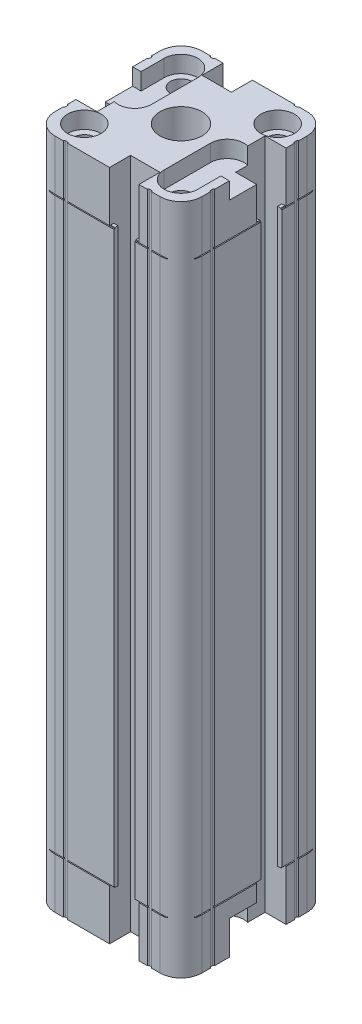
SolidWorks part; units mm, degrees
ref_plane "Front Plane" through (0, 0, 0) normal (0, 0, 1) x (1, 0, 0)
ref_plane "Top Plane" through (0, 0, 0) normal (0, 1, 0) x (1, 0, 0)
ref_plane "Right Plane" through (0, 0, 0) normal (1, 0, 0) x (0, 0, -1)
sketch "Sketch1" plane through (0, 0, 0) normal (0, 1, 0) x (1, 0, 0)
  line L1 (0, 0) -> (35, 0)
  line L2 (0, 0) -> (0, 35)
  line L3 (0, 35) -> (35, 35)
  line L4 (35, 0) -> (35, 35)
  dimension "D1" = 35
  dimension "D2" = 35
extrude "Boss-Extrude1" add sketch "Sketch1" along normal blind 160
sketch "Sketch2" plane through (0, 0, 0) normal (0, -1, 0) x (-1, 0, 0)
  line L0 (0, 0) -> (-35, 0) construction
  line L1 (0, 35) -> (0, 0) construction
  line L2 (-29, 6) -> (-29, 17) construction
  line L3 (-33, 6) -> (-33, 17)
  line L4 (-25, 6) -> (-25, 17)
  line L5 (-35, 0) -> (-35, 35) construction
  line L6 (-35, 35) -> (0, 35) construction
  line L7 (-6, 18) -> (-6, 29) construction
  line L8 (-10, 18) -> (-10, 29)
  line L9 (-2, 18) -> (-2, 29)
  circle A0 centre (-6, 6) radius 4
  circle A1 centre (-29, 29) radius 4
  arc A2 (-33, 6) -> (-25, 6) centre (-29, 6) ccw
  arc A3 (-25, 17) -> (-33, 17) centre (-29, 17) ccw
  arc A4 (-10, 18) -> (-2, 18) centre (-6, 18) ccw
  arc A5 (-2, 29) -> (-10, 29) centre (-6, 29) ccw
  point P10 (-29, 11.5)
  point P21 (-6, 23.5)
  dimension "D1" = 8
  dimension "D4" = 4
  dimension "D5" = 11
  dimension "D10" = 4
  dimension "D11" = 6
  dimension "D2" = 6
  dimension "D3" = 6
  dimension "D6" = 6
  dimension "D7" = 6
  dimension "D8" = 6
  dimension "D9" = 11
extrude "Cut-Extrude1" cut sketch "Sketch2" against normal blind 8
sketch "Sketch3" plane through (0, 0, 0) normal (0, -1, 0) x (-1, 0, 0)
  line L0 (0, 35) -> (0, 0) construction
  line L1 (-5, 23.5) -> (0, 23.5)
  line L2 (-5, 23.5) -> (-5, 14.127)
  line L3 (-5, 14.127) -> (0, 14.127)
  line L4 (0, 23.5) -> (0, 14.127)
  line L5 (-2, 18) -> (-2, 29) construction
  line L6 (-35, 20.873) -> (-30, 20.873)
  line L7 (-35, 20.873) -> (-35, 11.5)
  line L8 (-35, 11.5) -> (-30, 11.5)
  line L9 (-30, 20.873) -> (-30, 11.5)
  line L10 (-35, 0) -> (-35, 35) construction
  line L11 (-33, 17) -> (-33, 6) construction
  arc A2 (-25, 17) -> (-33, 17) centre (-29, 17) ccw construction
  arc A3 (-10, 18) -> (-2, 18) centre (-6, 18) ccw construction
  point P13 (-2, 23.5)
  point P25 (-32.5, 20.873)
  point P34 (-33, 11.5)
  dimension "D1" = 5
  dimension "D2" = 5
extrude "Cut-Extrude2" cut sketch "Sketch3" against normal up to surface (8 mm away) up to face at (6, 8, -23.5)
sketch "Sketch5" plane through (0, 0, 0) normal (0, -1, 0) x (1, 0, 0)
  line L0 (35, -20.873) -> (35, -35) construction
  line L1 (5, -17) -> (0, -17)
  line L2 (5, -17) -> (5, -10)
  line L3 (5, -10) -> (0, -10)
  line L4 (0, -17) -> (0, -10)
  line L5 (30, -18) -> (35, -18)
  line L6 (30, -18) -> (30, -25)
  line L7 (30, -25) -> (35, -25)
  line L8 (35, -18) -> (35, -25)
  line L9 (0, 0) -> (35, 0) construction
  line L10 (18, 0) -> (25, 0)
  line L11 (18, 0) -> (18, -5)
  line L12 (18, -5) -> (25, -5)
  line L13 (25, 0) -> (25, -5)
  line L14 (35, -35) -> (0, -35) construction
  line L15 (10, -35) -> (17, -35)
  line L16 (10, -35) -> (10, -30)
  line L17 (10, -30) -> (17, -30)
  line L18 (17, -35) -> (17, -30)
  circle A0 centre (6, -6) radius 4 construction
  circle A1 centre (29, -29) radius 4 construction
  dimension "D1" = 7
  dimension "D2" = 7
  dimension "D3" = 5
  dimension "D4" = 7
  dimension "D5" = 10
  dimension "D6" = 7
  dimension "D7" = 5
  dimension "D8" = 10
extrude "Cut-Extrude3" cut sketch "Sketch5" against normal blind 12
sketch "Sketch6" plane through (0, 12, 0) normal (0, -1, 0) x (1, 0, 0)
  line L6 (0, -16) -> (1, -16)
  line L7 (0, -10) -> (0, -17) construction
  line L8 (1, -16) -> (1, -17)
  line L9 (0, -17) -> (5, -17) construction
  line L10 (1, -17) -> (5, -17)
  line L11 (5, -17) -> (5, -10)
  line L12 (5, -10) -> (1, -10)
  line L13 (5, -10) -> (0, -10) construction
  line L14 (1, -10) -> (1, -11)
  line L15 (1, -11) -> (0, -11)
  line L16 (0, -11) -> (0, -16)
  line L17 (19, 0) -> (19, -1)
  line L18 (25, 0) -> (18, 0) construction
  line L19 (19, -1) -> (18, -1)
  line L20 (18, 0) -> (18, -5) construction
  line L21 (18, -1) -> (18, -5)
  line L22 (18, -5) -> (25, -5)
  line L23 (25, -5) -> (25, -1.01)
  line L24 (25, -5) -> (25, 0) construction
  line L25 (25, -1.01) -> (24, -1.01)
  line L26 (24, -1.01) -> (24, 0)
  line L27 (24, 0) -> (19, 0)
  line L28 (35, -19) -> (34, -19)
  line L29 (35, -25) -> (35, -18) construction
  line L30 (34, -19) -> (34, -18)
  line L31 (35, -18) -> (30, -18) construction
  line L32 (34, -18) -> (30, -18)
  line L33 (30, -18) -> (30, -25)
  line L34 (30, -25) -> (34, -25)
  line L35 (30, -25) -> (35, -25) construction
  line L36 (34, -25) -> (34, -24)
  line L37 (34, -24) -> (35, -24)
  line L38 (35, -24) -> (35, -19)
  line L39 (11, -35) -> (11, -34)
  line L40 (10, -35) -> (17, -35) construction
  line L41 (11, -34) -> (10, -34)
  line L42 (10, -30) -> (10, -35) construction
  line L43 (10, -34) -> (10, -30)
  line L44 (10, -30) -> (17, -30)
  line L45 (17, -30) -> (17, -34)
  line L46 (17, -35) -> (17, -30) construction
  line L47 (17, -34) -> (16, -34)
  line L48 (16, -34) -> (16, -35)
  line L49 (16, -35) -> (11, -35)
  dimension "D1" = 1
  dimension "D2" = 1
  dimension "D3" = 1
  dimension "D4" = 1
extrude "Cut-Extrude4" cut sketch "Sketch6" against normal blind 136
sketch "Sketch7" plane through (0, 160, 0) normal (0, 1, 0) x (1, 0, 0)
  line L0 (6, 29) -> (6, 18) construction
  line L1 (10, 29) -> (10, 18)
  line L2 (2, 29) -> (2, 18)
  line L3 (29, 17) -> (29, 6) construction
  line L4 (33, 17) -> (33, 6)
  line L5 (25, 17) -> (25, 6)
  arc A2 (10, 29) -> (2, 29) centre (6, 29) ccw
  arc A6 (2, 18) -> (10, 18) centre (6, 18) ccw
  circle A8 centre (29, 29) radius 4
  arc A9 (10, 29) -> (2, 29) centre (6, 29) ccw construction
  arc A10 (33, 17) -> (25, 17) centre (29, 17) ccw
  arc A11 (25, 6) -> (33, 6) centre (29, 6) ccw
  arc A12 (33, 17) -> (25, 17) centre (29, 17) ccw construction
  circle A13 centre (6, 6) radius 4
  point P4 (6, 23.5)
  point P14 (29, 11.5)
extrude "Cut-Extrude5" cut sketch "Sketch7" against normal blind 4
sketch "Sketch9" plane through (0, 160, 0) normal (0, 1, 0) x (1, 0, 0)
  line L1 (0, 23.5) -> (5, 23.5)
  line L2 (0, 23.5) -> (0, 14.127)
  line L3 (0, 14.127) -> (5, 14.127)
  line L4 (5, 23.5) -> (5, 14.127)
  line L5 (35, 20.873) -> (30, 20.873)
  line L6 (35, 20.873) -> (35, 11.5)
  line L7 (35, 11.5) -> (30, 11.5)
  line L8 (30, 20.873) -> (30, 11.5)
extrude "Cut-Extrude7" cut sketch "Sketch9" against normal up to surface (4 mm away) up to face at (6, 156, -23.5)
sketch "Sketch10" plane through (0, 160, 0) normal (0, 1, 0) x (1, 0, 0)
  line L1 (10, 30) -> (17, 30)
  line L2 (10, 30) -> (10, 35)
  line L3 (10, 35) -> (17, 35)
  line L4 (17, 30) -> (17, 35)
  line L5 (35, 25) -> (30, 25)
  line L6 (35, 25) -> (35, 18)
  line L7 (35, 18) -> (30, 18)
  line L8 (30, 25) -> (30, 18)
  line L9 (5, 10) -> (0, 10)
  line L10 (5, 10) -> (5, 17)
  line L11 (5, 17) -> (0, 17)
  line L12 (0, 10) -> (0, 17)
  line L13 (25, 5) -> (18, 5)
  line L14 (25, 5) -> (25, 0)
  line L15 (25, 0) -> (18, 0)
  line L16 (18, 5) -> (18, 0)
extrude "Cut-Extrude8" cut sketch "Sketch10" against normal up to surface (12 mm away) up to face at (1.75, 148, -13.5)
sketch "Sketch11" plane through (0, 160, 0) normal (0, 1, 0) x (1, 0, 0)
  line L0 (10, 35) -> (0, 35) construction
  line L1 (7, 35) -> (8, 35)
  line L2 (7, 35) -> (7, 34.75)
  line L3 (7, 34.75) -> (8, 34.75)
  line L4 (8, 35) -> (8, 34.75)
  line L5 (0, 35) -> (0, 23.5) construction
  line L6 (35, 35) -> (17, 35) construction
  line L7 (27, 35) -> (28, 35)
  line L8 (27, 35) -> (27, 34.75)
  line L9 (27, 34.75) -> (28, 34.75)
  line L10 (28, 35) -> (28, 34.75)
  line L11 (35, 25) -> (35, 35) construction
  line L12 (35, 0) -> (35, 11.5) construction
  line L13 (35, 28) -> (34.75, 28)
  line L14 (35, 28) -> (35, 27)
  line L15 (35, 27) -> (34.75, 27)
  line L16 (34.75, 28) -> (34.75, 27)
  line L17 (35, 8) -> (34.75, 8)
  line L18 (35, 8) -> (35, 7)
  line L19 (35, 7) -> (34.75, 7)
  line L20 (34.75, 8) -> (34.75, 7)
  line L21 (25, 0) -> (35, 0) construction
  line L22 (27, 0) -> (28, 0)
  line L23 (27, 0) -> (27, 0.25)
  line L24 (27, 0.25) -> (28, 0.25)
  line L25 (28, 0) -> (28, 0.25)
  line L26 (0, 0) -> (18, 0) construction
  line L27 (8, 0) -> (7, 0)
  line L28 (8, 0) -> (8, 0.25)
  line L29 (8, 0.25) -> (7, 0.25)
  line L30 (7, 0) -> (7, 0.25)
  line L31 (0, 10) -> (0, 0) construction
  line L32 (0, 8) -> (0.25, 8)
  line L33 (0, 8) -> (0, 7)
  line L34 (0, 7) -> (0.25, 7)
  line L35 (0.25, 8) -> (0.25, 7)
  line L36 (10, 35) -> (0, 35) construction
  line L37 (0, 28) -> (0.25, 28)
  line L38 (0, 28) -> (0, 27)
  line L39 (0, 27) -> (0.25, 27)
  line L40 (0.25, 28) -> (0.25, 27)
  dimension "D1" = 7
  dimension "D2" = 1
  dimension "D3" = 0.25
  dimension "D4" = 7
  dimension "D5" = 7
  dimension "D6" = 7
  dimension "D7" = 7
  dimension "D8" = 7
  dimension "D9" = 7
  dimension "D10" = 7
extrude "Cut-Extrude9" cut sketch "Sketch11" against normal through all
fillet "Fillet2" radius 0.25 16 edges at (0.25, 80, -7) (0.25, 80, -8) (7, 80, -0.25) (8, 80, -0.25) (28, 80, -0.25) (27, 80, -0.25) (34.75, 80, -8) (34.75, 80, -7) (34.75, 80, -27) (34.75, 80, -28) (27, 80, -34.75) (28, 80, -34.75) (7, 80, -34.75) (8, 80, -34.75) (0.25, 80, -27) (0.25, 80, -28)
sketch "Sketch12" plane through (0, 0, 0) normal (-1, 0, 0) x (0, 0, 1)
  line L0 (-35, 160) -> (-35, 0) construction
  line L1 (-35, 12.25) -> (-34.75, 12.25)
  line L2 (-35, 12.25) -> (-35, 12)
  line L3 (-35, 12) -> (-34.75, 12)
  line L4 (-34.75, 12.25) -> (-34.75, 12)
  line L5 (0, 160) -> (0, 0) construction
  line L6 (0, 12.25) -> (-0.25, 12.25)
  line L7 (0, 12.25) -> (0, 12)
  line L8 (0, 12) -> (-0.25, 12)
  line L9 (-0.25, 12.25) -> (-0.25, 12)
  line L10 (-35, 0) -> (-28, 0) construction
  line L11 (-7, 0) -> (0, 0) construction
  line L12 (-35, 160) -> (-28, 160) construction
  line L13 (-35, 148) -> (-34.75, 148)
  line L14 (-35, 148) -> (-35, 147.75)
  line L15 (-35, 147.75) -> (-34.75, 147.75)
  line L16 (-34.75, 148) -> (-34.75, 147.75)
  line L17 (0, 148) -> (-0.25, 148)
  line L18 (0, 148) -> (0, 147.75)
  line L19 (0, 147.75) -> (-0.25, 147.75)
  line L20 (-0.25, 148) -> (-0.25, 147.75)
  line L21 (-7, 160) -> (0, 160) construction
  dimension "D1" = 0.25
  dimension "D2" = 0.25
  dimension "D3" = 0.25
  dimension "D4" = 0.25
  dimension "D5" = 12
  dimension "D6" = 12
  dimension "D7" = 0.25
  dimension "D8" = 0.25
  dimension "D9" = 0.25
  dimension "D10" = 0.25
  dimension "D11" = 12
  dimension "D12" = 12
fillet "Fillet4" radius 5 4 edges at (35, 80, 0) (0, 80, 0) (35, 80, -35) (0, 80, -35)
extrude "Cut-Extrude12" cut sketch "Sketch12" against normal through all
sketch "Sketch14" plane through (0, 0, 0) normal (0, 0, 1) x (1, 0, 0)
  line L0 (35, 160) -> (35, 0) construction
  line L1 (0, 148) -> (0.25, 148)
  line L2 (0, 148) -> (0, 147.75)
  line L3 (0, 147.75) -> (0.25, 147.75)
  line L4 (0.25, 148) -> (0.25, 147.75)
  line L9 (0, 12.25) -> (0, 12) construction
  line L10 (0, 12.25) -> (0.25, 12.25)
  line L11 (0, 12.25) -> (0, 12)
  line L12 (0, 12) -> (0.25, 12)
  line L13 (0.25, 12.25) -> (0.25, 12)
  line L14 (0, 12.25) -> (0, 12) construction
  line L16 (35, 12.25) -> (34.75, 12.25)
  line L17 (35, 12.25) -> (35, 12)
  line L18 (35, 12) -> (34.75, 12)
  line L19 (34.75, 12.25) -> (34.75, 12)
  line L20 (35, 147.75) -> (34.75, 147.75)
  line L21 (35, 147.75) -> (35, 148)
  line L22 (35, 148) -> (34.75, 148)
  line L23 (34.75, 147.75) -> (34.75, 148)
  dimension "D1" = 0.25
  dimension "D2" = 0.25
  dimension "D3" = 0.25
  dimension "D5" = 0.25
  dimension "D6" = 0.25
  dimension "D7" = 0.25
  dimension "D8" = 0.25
extrude "Cut-Extrude13" cut sketch "Sketch14" against normal through all
sketch "Sketch15" plane through (0, 8, 0) normal (0, -1, 0) x (-1, 0, 0)
  circle A0 centre (-6, 6) radius 2.5
  circle A1 centre (-29, 29) radius 2.5
  circle A3 centre (-29, 6) radius 2.5
  circle A4 centre (-6, 29) radius 2.5
  dimension "D1" = 5
extrude "Cut-Extrude14" cut sketch "Sketch15" against normal up to vertex (4 mm away) up to point (0.25, 12, -3.4388)
thread "Thread2" pitch 0.8 method extrude profile "Thread Profile2" start angle 0, offset 0, length 0, pitch 0.8, diameter 5
ref_plane "Plane2" through (31.5, 8, -6) normal (0, 0, 1) x (1, 0, 0)
sketch "Thread Profile2" plane through (31.5, 8, -6) normal (0, 0, 1) x (1, 0, 0)
  line L0 (0, 0) -> (0, 0.8) construction
  line L11 (0, 0) -> (0, 0.7)
  line L12 (0, 0.7) -> (-0.433, 0.45)
  line L13 (-0.433, 0.45) -> (-0.433, 0.25)
  line L15 (-0.433, 0.25) -> (0, 0)
  line L17 (-0.433, 0.35) -> (0, 0.35) construction
  point P2 (0, 0)
  dimension "Pitch" = 0.8
  dimension "Profile_Angle" = 60
  dimension "Profile_Land" = 0.2
  dimension "Profile_Height" = 0.433
thread "Thread3" pitch 0.8 method extrude profile "Thread Profile3" start angle 0, offset 0, length 0, pitch 0.8, diameter 5
ref_plane "Plane3" through (8.5, 8, -29) normal (0, 0, 1) x (1, 0, 0)
sketch "Thread Profile3" plane through (8.5, 8, -29) normal (0, 0, 1) x (1, 0, 0)
  line L0 (0, 0) -> (0, 0.8) construction
  line L11 (0, 0) -> (0, 0.7)
  line L12 (0, 0.7) -> (-0.433, 0.45)
  line L13 (-0.433, 0.45) -> (-0.433, 0.25)
  line L15 (-0.433, 0.25) -> (0, 0)
  line L17 (-0.433, 0.35) -> (0, 0.35) construction
  point P2 (0, 0)
  dimension "Pitch" = 0.8
  dimension "Profile_Angle" = 60
  dimension "Profile_Land" = 0.2
  dimension "Profile_Height" = 0.433
sketch "Sketch24" plane through (0, 156, 0) normal (0, 1, 0) x (1, 0, 0)
  circle A0 centre (6, 29) radius 2.5
  circle A1 centre (29, 29) radius 2.5
  circle A2 centre (6, 6) radius 2.5
  circle A3 centre (29, 6) radius 2.5
  dimension "D1" = 5
extrude "Cut-Extrude15" cut sketch "Sketch24" against normal up to vertex (144 mm away) up to point (18, 12, 0)
sketch "Sketch33" plane through (0, 0, 0) normal (0, -1, 0) x (-1, 0, 0)
  line L0 (-35, 11.5) -> (-35, 18) construction
  line L1 (-8, 0) -> (-18, 0) construction
  circle A0 centre (-17.5, 17.5) radius 6
  dimension "D1" = 12
  dimension "D2" = 17.5
  dimension "D3" = 17.5
extrude "Cut-Extrude16" cut sketch "Sketch33" against normal blind 3
sketch "Sketch35" plane through (0, 160, 0) normal (0, 1, 0) x (1, 0, 0)
  line L0 (27, 35) -> (17, 35) construction
  line L1 (0, 17) -> (0, 23.5) construction
  circle A0 centre (17.5, 17.5) radius 5
  dimension "D1" = 10
  dimension "D2" = 17.5
  dimension "D3" = 17.5
ref_plane "Plane4" through (0, 147.75, 0) normal (0, -1, 0) x (-1, 0, 0)
sketch "Sketch36" plane through (0, 147.75, 0) normal (0, -1, 0) x (-1, 0, 0)
  line L0 (-35, 25) -> (-35, 27) construction
  line L1 (-26.5, 26.5) -> (-8.5, 26.5)
  line L2 (-26.5, 26.5) -> (-26.5, 8.5)
  line L3 (-26.5, 8.5) -> (-8.5, 8.5)
  line L4 (-8.5, 26.5) -> (-8.5, 8.5)
  line L5 (-8, 0) -> (-18, 0) construction
  dimension "D1" = 18
  dimension "D2" = 18
  dimension "D3" = 8.5
  dimension "D4" = 8.5
extrude "Cut-Extrude17" cut sketch "Sketch36" along normal blind 130
extrude "Cut-Extrude18" cut sketch "Sketch35" against normal up to next contours A0
